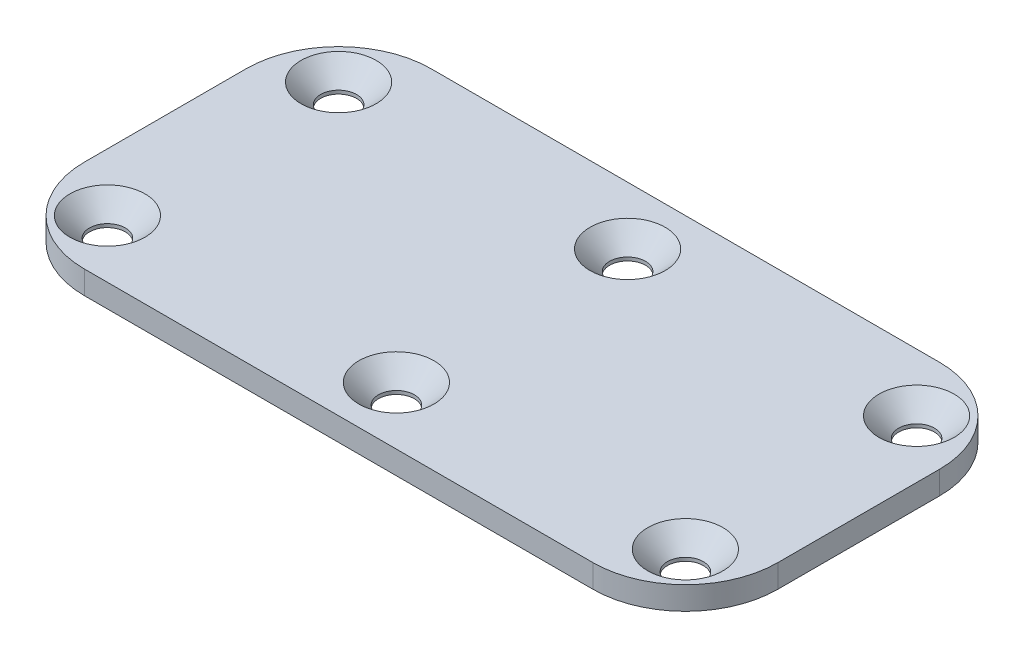
SolidWorks part; units mm, degrees
material "6063-T6"
ref_plane "Front Plane" through (0, 0, 0) normal (0, 0, 1) x (1, 0, 0)
ref_plane "Top Plane" through (0, 0, 0) normal (0, 1, 0) x (1, 0, 0)
ref_plane "Right Plane" through (0, 0, 0) normal (1, 0, 0) x (0, 0, -1)
sketch "Sketch1" plane through (0, 0, 0) normal (0, 1, 0) x (1, 0, 0)
  line L1 (22, -15) -> (-22, -15)
  line L2 (30, -7) -> (30, 7)
  line L3 (22, 15) -> (-22, 15)
  line L4 (-30, -7) -> (-30, 7)
  line L5 (30, -15) -> (-30, 15) construction
  line L6 (30, 15) -> (-30, -15) construction
  arc A0 (30, 7) -> (22, 15) centre (22, 7) ccw
  arc A1 (22, -15) -> (30, -7) centre (22, -7) ccw
  arc A2 (-22, -15) -> (-30, -7) centre (-22, -7) cw
  arc A3 (-22, 15) -> (-30, 7) centre (-22, 7) ccw
  point P0 (0, 0)
  dimension "D3" = 8
  dimension "D1" = 60
  dimension "D2" = 30
extrude "Boss-Extrude1" add sketch "Sketch1" along normal blind 2
hole_wizard "Ø3.1 (3.1) Diameter Hole1" positions "Sketch2" profile "Sketch3" hole size "Ø3.1" standard "ANSI Metric" end condition through all
sketch "Sketch2" plane through (0, 2, 0) normal (0, -1, 0) x (-1, 0, 0)
  line L4 (-33.1926, 0) -> (33.4931, 0) construction
  line L6 (0, 17.9223) -> (0, -17.6691) construction
  point P0 (-25, 10)
  point P2 (-25, -10)
  point P4 (25, -10)
  point P6 (25, 10)
  point P29 (0, 10)
  point P31 (0, -10)
  dimension "D1" = 20
  dimension "D2" = 25
  dimension "D3" = 25
sketch "Sketch3" plane through (25, 2, -10) normal (1, 0, 0) x (0, 0, 1)
  line L0 (0, 0) -> (0, 2)
  line L1 (0, 2) -> (1.55, 2)
  line L2 (1.55, 2) -> (1.55, 1.7)
  line L3 (1.55, 1.7) -> (3.25, 0)
  line L5 (3.25, 0) -> (0, 0)
  line L6 (-1.55, 1.7) -> (-3.25, 0) construction
  line L11 (0, -6.35) -> (0, 107.95) construction
  dimension "Thru Hole Dia." = 3.1
  dimension "Thru Hole Depth" = 2
  dimension "Near C'Sink Dia." = 6.5
  dimension "Near C'Sink Angle" = 90
